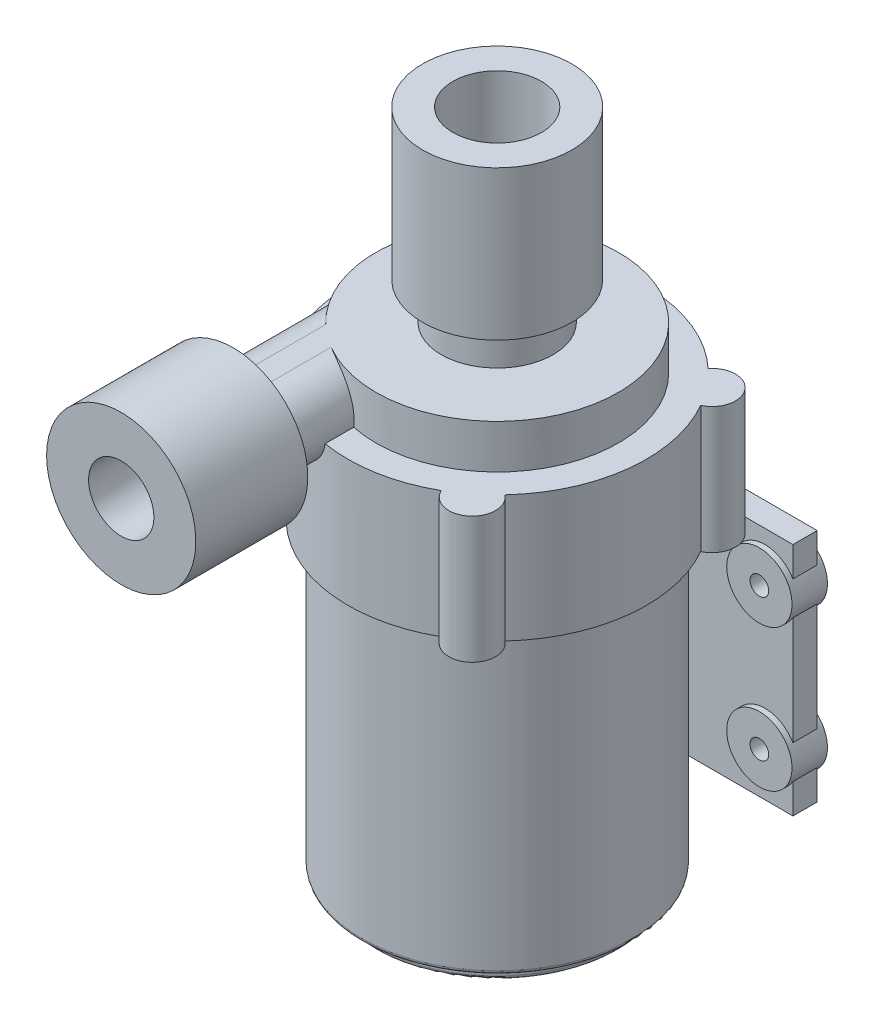
SolidWorks part; units mm, degrees
note: The reader was unsure of these and kept them because the rebuilt part matched: shared geometry of "Sketch3<2>", "Sketch5<4>", "Sketch10<2>".
ref_plane "Front Plane" through (0, 0, 0) normal (0, 0, 1) x (1, 0, 0)
ref_plane "Top Plane" through (0, 0, 0) normal (0, 1, 0) x (1, 0, 0)
ref_plane "Right Plane" through (0, 0, 0) normal (1, 0, 0) x (0, 0, -1)
sketch "Sketch1" plane through (0, 0, 0) normal (0, 1, 0) x (1, 0, 0)
  circle A0 centre (0, 0) radius 18.415
  dimension "D1" = 36.83
extrude "Boss-Extrude1" add sketch "Sketch1" along normal blind 42.672
sketch "Sketch2" plane through (0, 0, 0) normal (0, -1, 0) x (1, 0, 0)
  circle A0 centre (0, 0) radius 16.51
  dimension "D1" = 33.02
extrude "Cut-Extrude2" cut sketch "Sketch2" against normal blind 1.9431 flip side to cut
fillet "Fillet1" radius 0.508 3 edges at (0, 0, -16.51) (0, 1.9431, -16.51) (0, 1.9431, -18.415)
ref_plane "Plane1" through (0, 0, -18.415) normal (0, 0, -1) x (-1, 0, 0)
sketch "Sketch3" plane through (0, 0, -18.415) normal (0, 0, -1) x (-1, 0, 0)
  line L0 (0, 20.2565) -> (0, -20.2565) construction
  line L1 (-22.606, 42.164) -> (22.606, 42.164)
  line L2 (-22.606, 42.164) -> (-22.606, 10.16)
  line L3 (-22.606, 10.16) -> (22.606, 10.16)
  line L4 (22.606, 42.164) -> (22.606, 10.16)
  line L5 (-22.606, 42.164) -> (22.606, 10.16) construction
  line L6 (-22.606, 10.16) -> (22.606, 42.164) construction
  line L7 (20.2565, 0) -> (-20.2565, 0) construction
  line L8 (0, 40.019) -> (0, 11.6806) construction
  line L9 (-16.1476, 26.162) -> (14.9918, 26.162) construction
  circle A0 centre (-18.796, 35.814) radius 1.27
  circle A1 centre (-18.796, 16.51) radius 1.27
  circle A2 centre (18.796, 16.51) radius 1.27
  circle A3 centre (18.796, 35.814) radius 1.27
  point P0 (0, 26.162)
  dimension "D4" = 3.81
  dimension "D5" = 6.35
  dimension "D6" = 2.54
  dimension "D1" = 45.212
  dimension "D2" = 32.004
  dimension "D3" = 10.16
extrude "Boss-Extrude2" add sketch "Sketch3" along normal blind 2.54 separate body
extrude "Boss-Extrude3" add sketch "Sketch3<2>" against normal blind 0.762
sketch "Sketch3<2>" plane through (0, 0, -18.415) normal (0, 0, -1) x (-1, 0, 0) same geometry as "Sketch3"
sketch "Sketch5" plane through (0, 0, -20.955) normal (0, 0, -1) x (-1, 0, 0)
  line L0 (0, 29.7521) -> (0, 16.51) construction
  line L1 (0, 42.672) -> (0, 2.4511) construction
  circle A0 centre (-18.796, 35.814) radius 4.445
  circle A1 centre (-18.796, 35.814) radius 1.27
  circle A2 centre (-18.796, 16.51) radius 1.27
  circle A3 centre (-18.796, 16.51) radius 4.445
  circle A4 centre (18.796, 16.51) radius 4.445
  circle A5 centre (18.796, 16.51) radius 1.27
  circle A6 centre (18.796, 35.814) radius 1.27
  circle A7 centre (18.796, 35.814) radius 4.445
  dimension "D1" = 8.89
extrude "Boss-Extrude5" add sketch "Sketch5" along normal blind 0.762
extrude "Boss-Extrude8" add sketch "Sketch5<4>" against normal blind 4.064
sketch "Sketch5<4>" plane through (0, 0, -20.955) normal (0, 0, -1) x (-1, 0, 0) same geometry as "Sketch5"
sketch "Sketch6" plane through (0, 42.672, 0) normal (0, 1, 0) x (1, 0, 0)
  arc A0 (-14.8858, 13.8316) -> (-17.6632, -10.0456) centre (0, 0) ccw
  arc A1 (15.2593, -14.176) -> (-18.1058, -10.295) centre (0, 0) ccw construction
  arc A2 (-10.0456, 17.6632) -> (-14.8858, 13.8316) centre (-12.9274, 16.3306) ccw
  arc A3 (17.6632, 10.0456) -> (13.8316, 14.8858) centre (16.3306, 12.9274) ccw
  arc A4 (10.0456, -17.6632) -> (14.8858, -13.8316) centre (12.9274, -16.3306) ccw
  arc A5 (-17.6632, -10.0456) -> (-13.8316, -14.8858) centre (-16.3306, -12.9274) ccw
  arc A6 (13.8316, 14.8858) -> (-10.0456, 17.6632) centre (0, 0) ccw
  arc A7 (14.8858, -13.8316) -> (17.6632, 10.0456) centre (0, 0) ccw
  arc A8 (-14.176, -15.2593) -> (10.295, -18.1058) centre (0, 0) ccw construction
  arc A9 (-13.8316, -14.8858) -> (10.0456, -17.6632) centre (0, 0) ccw
  point P15 (0, 0)
  dimension "D1" = 40.64
  dimension "D2" = 41.656
  dimension "D3" = 6.35
  dimension "D4" = 4
extrude "Boss-Extrude9" add sketch "Sketch6" along normal blind 17.2339
sketch "Sketch7" plane through (0, 59.9059, 0) normal (0, 1, 0) x (1, 0, 0)
  circle A0 centre (0, 0) radius 16.51
  dimension "D1" = 33.02
extrude "Boss-Extrude10" add sketch "Sketch7" along normal blind 5.969
sketch "Sketch8" plane through (0, 65.8749, 0) normal (0, 1, 0) x (1, 0, 0)
  circle A0 centre (0, 0) radius 7.62
  dimension "D1" = 15.24
extrude "Boss-Extrude11" add sketch "Sketch8" along normal blind 5.08
sketch "Sketch9" plane through (0, 70.9549, 0) normal (0, 1, 0) x (1, 0, 0)
  circle A0 centre (0, 0) radius 10.16
  circle A1 centre (0, 0) radius 6.0325
  dimension "D1" = 20.32
  dimension "D2" = 12.065
extrude "Boss-Extrude12" add sketch "Sketch9" along normal blind 20.32
ref_plane "Plane6" through (0, 0, 16.51) normal (0, 0, 1) x (1, 0, 0)
sketch "Sketch10" plane through (0, 0, 16.51) normal (0, 0, 1) x (1, 0, 0)
  line L0 (-11.43, 60.7949) -> (-8.382, 60.7949) construction
  line L1 (-11.43, 65.8749) -> (-8.382, 65.8749)
  line L2 (-11.43, 55.7149) -> (-8.382, 55.7149)
  line L3 (16.51, 65.8749) -> (-16.51, 65.8749) construction
  line L4 (-16.51, 65.8749) -> (-16.51, 59.9059) construction
  line L6 (-16.51, 65.8749) -> (-3.175, 65.8749) construction
  line L7 (-16.51, 65.8749) -> (-16.51, 55.7149) construction
  line L8 (-16.51, 55.7149) -> (-3.175, 55.7149) construction
  line L9 (-3.175, 65.8749) -> (-3.175, 55.7149) construction
  arc A0 (-11.43, 65.8749) -> (-11.43, 55.7149) centre (-11.43, 60.7949) ccw
  arc A1 (-8.382, 55.7149) -> (-8.382, 65.8749) centre (-8.382, 60.7949) ccw
  point P2 (-9.906, 60.7949)
  point P11 (-16.51, 60.7949)
  dimension "D4" = 13.335
  dimension "D1" = 10.16
  dimension "D2" = 0
  dimension "D3" = 0
  dimension "D5" = 3.048
extrude "Boss-Extrude13" add sketch "Sketch10" against normal up to next
extrude "Boss-Extrude14" add sketch "Sketch10<2>" along normal blind 9.525
sketch "Sketch10<2>" plane through (0, 0, 16.51) normal (0, 0, 1) x (1, 0, 0) same geometry as "Sketch10"
sketch "Sketch11" plane through (0, 0, 26.035) normal (0, 0, 1) x (1, 0, 0)
  circle A0 centre (-9.906, 60.7949) radius 10.16
  circle A1 centre (-9.906, 60.7949) radius 4.445
  dimension "D1" = 8.89
  dimension "D2" = 20.32
extrude "Boss-Extrude17" add sketch "Sketch11" along normal blind 15.24
